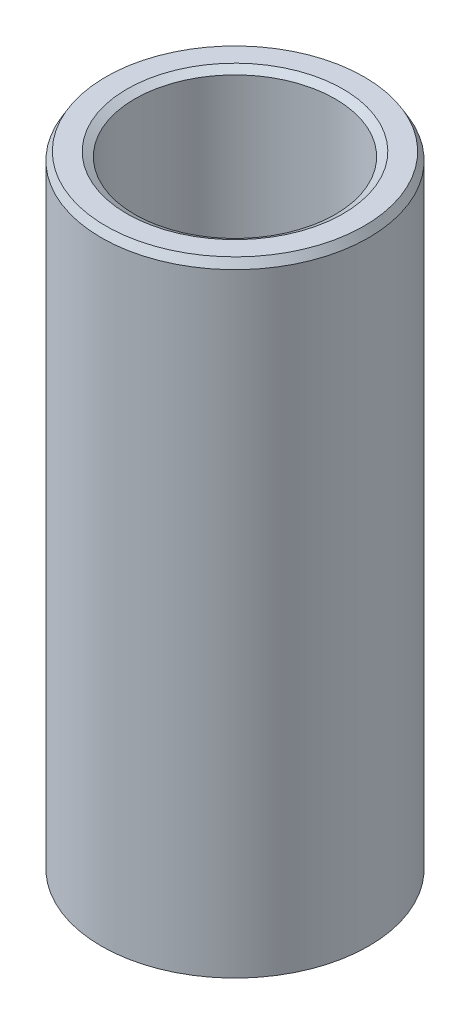
SolidWorks part; units mm, degrees
ref_plane "Front Plane" through (0, 0, 0) normal (0, 0, 1) x (1, 0, 0)
ref_plane "Top Plane" through (0, 0, 0) normal (0, 1, 0) x (1, 0, 0)
ref_plane "Right Plane" through (0, 0, 0) normal (1, 0, 0) x (0, 0, -1)
sketch "Sketch1" plane through (0, 0, 0) normal (0, 1, 0) x (1, 0, 0)
  circle A0 centre (0, 0) radius 55
  dimension "SLEEVE_OD" = 110
extrude "Boss-Extrude1" add sketch "Sketch1" along normal blind 257.4286
sketch "Sketch2" plane through (0, 0, 0) normal (0, 1, 0) x (1, 0, 0)
  circle A0 centre (0, 0) radius 41.2039
  dimension "BORE_D" = 82.4078
extrude "Cut-Extrude1" cut sketch "Sketch2" along normal through all
chamfer "Chamfer1" distance 3.2417 angle 30 4 edges at (0, 257.4286, 41.2039) (0, 0, 41.2039) (0, 0, 55) (0, 257.4286, 55) first distance on face at (0, 257.4286, 41.2039) first distance on face at (0, 0, 41.2039) first distance on face at (0, 257.4286, 55)
